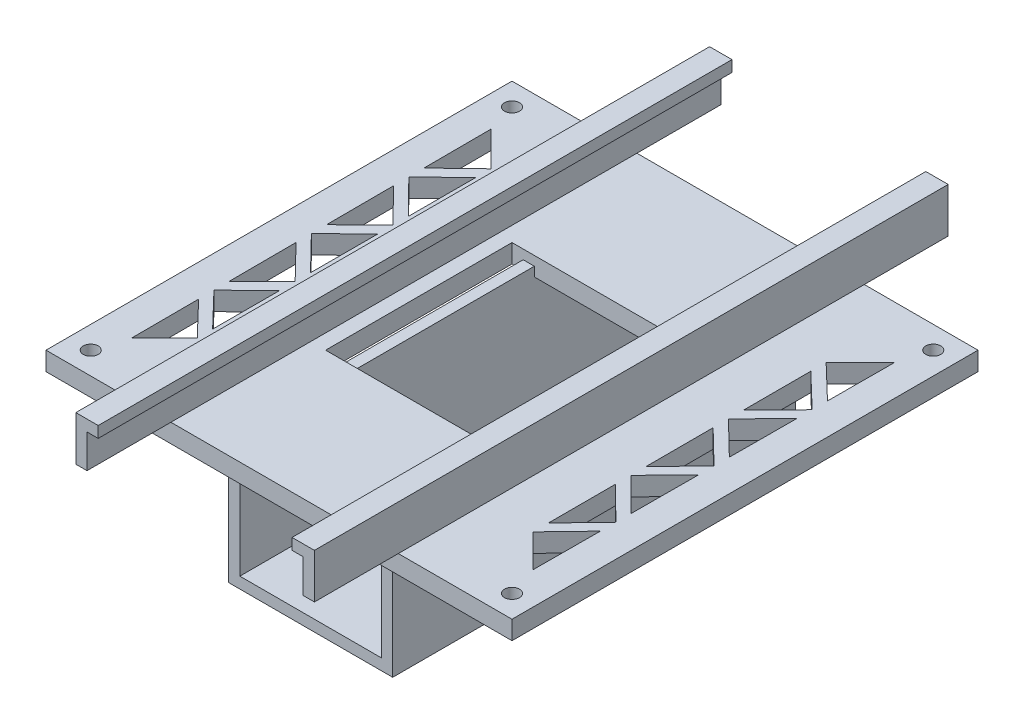
SolidWorks part; units mm, degrees
other "마크업1"
sketch "스케치10" plane through (-62.5, -31.5, -62.5) normal (-0.0294, -0.9842, -0.1746) x (0.6542, 0.1131, -0.7478)
ref_plane "정면" through (0, 0, 0) normal (0, 0, 1) x (1, 0, 0)
ref_plane "윗면" through (0, 0, 0) normal (0, 1, 0) x (1, 0, 0)
ref_plane "우측면" through (0, 0, 0) normal (1, 0, 0) x (0, 0, -1)
ref_axis "기준축1" through (0, 4.2, 0) along (0, -1, 0)
sketch "스케치2" plane through (0, 0, 0) normal (0, 1, 0) x (1, 0, 0)
  line L1 (62.5, 62.5) -> (-62.5, 62.5)
  line L2 (62.5, 62.5) -> (62.5, -62.5)
  line L3 (62.5, -62.5) -> (-62.5, -62.5)
  line L4 (-62.5, 62.5) -> (-62.5, -62.5)
  line L5 (62.5, 62.5) -> (-62.5, -62.5) construction
  line L6 (62.5, -62.5) -> (-62.5, 62.5) construction
  line L7 (-25, 25) -> (25, 25)
  line L8 (-25, 25) -> (-25, -25)
  line L9 (-25, -25) -> (25, -25)
  line L10 (25, 25) -> (25, -25)
  line L11 (-25, 25) -> (25, -25) construction
  line L12 (-25, -25) -> (25, 25) construction
  circle A0 centre (-56.5, 56.5) radius 2
  circle A1 centre (56.5, 56.5) radius 2
  circle A2 centre (-56.5, -56.5) radius 2
  circle A3 centre (56.5, -56.5) radius 2
  point P0 (0, 0)
  point P6 (0, 0)
  dimension "D5" = 4
  dimension "D1" = 125
  dimension "D2" = 125
  dimension "D3" = 50
  dimension "D4" = 50
  dimension "D6" = 6
  dimension "D7" = 6
  dimension "D8" = 6
  dimension "D9" = 6
extrude "보스-돌출1" add sketch "스케치2" along normal mid plane 5
sketch "스케치6" plane through (0, 0, 0) normal (0, 0, 1) x (1, 0, 0)
  line L0 (0, 0) -> (50000, 0) construction
  line L2 (0, 0) -> (0, -50000) construction
  line L3 (-22, 0) -> (-22, -35.5)
  line L4 (-22, -35.5) -> (22, -35.5)
  line L6 (19, -32.5) -> (-19, -32.5)
  line L7 (-19, -32.5) -> (-19, 0)
  line L8 (-19, 0) -> (-22, 0)
  line L9 (19, 0) -> (22, 0)
  line L10 (19, -32.5) -> (19, 0)
  line L11 (22, 0) -> (22, -35.5)
  line L12 (-62.5, -2.5) -> (62.5, -2.5) construction
  point P14 (0, -32.5)
  point P15 (0, -35.5)
  dimension "D1" = 38
  dimension "D2" = 3
  dimension "D3" = 30
  dimension "D4" = 3
extrude "보스-돌출4" add sketch "스케치6" along normal mid plane 108
sketch "스케치11" plane through (0, 0, 0) normal (0, 0, 1) x (1, 0, 0)
  line L0 (-32, 2.5) -> (-32, 14.5)
  line L1 (-62.5, 2.5) -> (62.5, 2.5) construction
  line L2 (-32, 14.5) -> (-26, 14.5)
  line L3 (-26, 14.5) -> (-26, 11.5)
  line L4 (-26, 11.5) -> (-29, 11.5)
  line L5 (-29, 11.5) -> (-29, 2.5)
  line L6 (-32, 2.5) -> (-29, 2.5)
  line L7 (0, -25.3) -> (0, 25.3) construction
  line L8 (32, 2.5) -> (29, 2.5)
  line L9 (29, 11.5) -> (29, 2.5)
  line L10 (26, 11.5) -> (29, 11.5)
  line L11 (26, 14.5) -> (26, 11.5)
  line L12 (32, 14.5) -> (26, 14.5)
  line L13 (32, 2.5) -> (32, 14.5)
  point P8 (-26, 13)
  dimension "D1" = 29
  dimension "D2" = 3
  dimension "D3" = 9
  dimension "D4" = 3
  dimension "D5" = 6
sketch "스케치7" plane through (0, 0, 0) normal (0, 1, 0) x (1, 0, 0)
  line L1 (-40, 40) -> (40, 40)
  line L2 (-40, 40) -> (-40, -40)
  line L3 (-40, -40) -> (40, -40)
  line L4 (40, 40) -> (40, -40)
  line L5 (-40, 40) -> (40, -40) construction
  line L6 (-40, -40) -> (40, 40) construction
  point P0 (0, 0)
  dimension "D1" = 80
  dimension "D2" = 80
extrude "컷-돌출1" [suppressed] cut sketch "스케치7" along normal blind 10
sketch "스케치8" plane through (0, 2.5, 0) normal (0, 1, 0) x (1, 0, 0)
  line L14 (54.1085, 30.5155) -> (54.094, 26.4186) construction
  line L15 (54.0793, 22.2856) -> (54.0155, 4.2857)
  line L20 (44.9633, 35.1872) -> (44.959, 39.3022) construction
  line L41 (53.8296, -48.1728) -> (45.0411, -39.3843)
  line L42 (45.0368, -35.2728) -> (45.018, -17.2728)
  line L43 (44.959, 39.3022) -> (54.1723, 48.5154)
  line L44 (54.1723, 48.5154) -> (54.1085, 30.5155)
  line L83 (62.5, -62.5) -> (-62.5, 62.5) construction
  line L94 (62.5, 62.5) -> (-62.5, -62.5) construction
  line L96 (45.0411, -39.3843) -> (53.8934, -30.1704)
  line L97 (45.0368, -35.2728) -> (53.9081, -26.0392)
  line L98 (53.9081, -26.0392) -> (45.018, -17.2728)
  line L100 (53.9226, -21.9404) -> (45.0138, -13.1555)
  line L101 (45.0138, -13.1555) -> (53.9864, -3.9443)
  line L103 (45.0095, -9.0428) -> (54.001, 0.1878)
  line L104 (54.001, 0.1878) -> (44.9907, 8.9572)
  line L106 (44.9864, 13.0733) -> (54.0155, 4.2857)
  line L107 (44.9864, 13.0733) -> (54.0793, 22.2856)
  line L108 (44.9821, 17.1872) -> (54.094, 26.4186)
  line L110 (54.094, 26.4186) -> (44.9633, 35.1872)
  line L112 (54.1085, 30.5155) -> (44.959, 39.3022)
  line L113 (44.9864, 13.0733) -> (44.9821, 17.1872) construction
  line L114 (44.9821, 17.1872) -> (44.9633, 35.1872)
  line L115 (54.094, 26.4186) -> (54.0793, 22.2856) construction
  line L116 (44.9907, 8.9572) -> (44.9864, 13.0733) construction
  line L117 (54.001, 0.1878) -> (53.9864, -3.9443) construction
  line L118 (53.9864, -3.9443) -> (53.9226, -21.9404)
  line L119 (54.0155, 4.2857) -> (54.001, 0.1878) construction
  line L120 (45.0138, -13.1555) -> (45.0095, -9.0428) construction
  line L121 (45.0095, -9.0428) -> (44.9907, 8.9572)
  line L122 (45.0411, -39.3843) -> (45.0368, -35.2728) construction
  line L123 (53.9081, -26.0392) -> (53.8934, -30.1704) construction
  line L124 (53.8934, -30.1704) -> (53.8296, -48.1728)
  line L125 (53.9226, -21.9404) -> (53.9081, -26.0392) construction
  line L126 (45.018, -17.2728) -> (45.0138, -13.1555) construction
  line L146 (0, -25.3) -> (0, 25.3) construction
  line L155 (-45.018, -17.2728) -> (-45.0138, -13.1555) construction
  line L156 (-53.9226, -21.9404) -> (-53.9081, -26.0392) construction
  line L157 (-53.9081, -26.0392) -> (-53.8934, -30.1704) construction
  line L158 (-45.0411, -39.3843) -> (-45.0368, -35.2728) construction
  line L159 (-45.0138, -13.1555) -> (-45.0095, -9.0428) construction
  line L160 (-54.0155, 4.2857) -> (-54.001, 0.1878) construction
  line L161 (-54.001, 0.1878) -> (-53.9864, -3.9443) construction
  line L162 (-44.9907, 8.9572) -> (-44.9864, 13.0733) construction
  line L163 (-54.094, 26.4186) -> (-54.0793, 22.2856) construction
  line L164 (-44.9864, 13.0733) -> (-44.9821, 17.1872) construction
  line L165 (-44.9633, 35.1872) -> (-44.959, 39.3022) construction
  line L166 (-54.1085, 30.5155) -> (-54.094, 26.4186) construction
  line L178 (-53.8934, -30.1704) -> (-53.8296, -48.1728)
  line L179 (-45.0095, -9.0428) -> (-44.9907, 8.9572)
  line L180 (-53.9864, -3.9443) -> (-53.9226, -21.9404)
  line L181 (-44.9821, 17.1872) -> (-44.9633, 35.1872)
  line L182 (-54.1085, 30.5155) -> (-44.959, 39.3022)
  line L183 (-54.094, 26.4186) -> (-44.9633, 35.1872)
  line L184 (-44.9821, 17.1872) -> (-54.094, 26.4186)
  line L185 (-44.9864, 13.0733) -> (-54.0793, 22.2856)
  line L186 (-44.9864, 13.0733) -> (-54.0155, 4.2857)
  line L187 (-54.001, 0.1878) -> (-44.9907, 8.9572)
  line L188 (-45.0095, -9.0428) -> (-54.001, 0.1878)
  line L189 (-45.0138, -13.1555) -> (-53.9864, -3.9443)
  line L190 (-53.9226, -21.9404) -> (-45.0138, -13.1555)
  line L191 (-53.9081, -26.0392) -> (-45.018, -17.2728)
  line L192 (-45.0368, -35.2728) -> (-53.9081, -26.0392)
  line L193 (-45.0411, -39.3843) -> (-53.8934, -30.1704)
  line L194 (-54.1723, 48.5154) -> (-54.1085, 30.5155)
  line L195 (-44.959, 39.3022) -> (-54.1723, 48.5154)
  line L196 (-45.0368, -35.2728) -> (-45.018, -17.2728)
  line L197 (-53.8296, -48.1728) -> (-45.0411, -39.3843)
  line L202 (-54.0793, 22.2856) -> (-54.0155, 4.2857)
  dimension "D3" = 45
  dimension "D4" = 54
  dimension "D5" = 4
  dimension "D6" = 4
  dimension "D9" = 8.23
  dimension "D10" = 4.115
  dimension "D11" = 18
  dimension "D7" = 18
  dimension "D13" = 8.23
  dimension "D14" = 18
  dimension "D16" = 8.23
  dimension "D17" = 18
  dimension "D19" = 8.23
  dimension "D20" = 8.23
  dimension "D21" = 17.9963
  dimension "D22" = 18
  dimension "D23" = 18.0024
extrude "컷-돌출2" cut sketch "스케치8" against normal blind 5 and the other way through all
pattern_circular "원형 패턴1" [suppressed] count 4 over 360 about axis through (0, 4.2, 0) along (0, -1, 0) of bodies 108
extrude "보스-돌출7" add sketch "스케치11" along normal mid plane 170
sketch "스케치9" [suppressed] plane through (0, 2.5, 0) normal (0, 1, 0) x (1, 0, 0)
  line L0 (-39.3431, -45) -> (-49.8431, -55.5)
  line L1 (-49.8431, -55.5) -> (-24, -55.5)
  line L2 (-24, -55.5) -> (-24, -45)
  line L3 (-24, -45) -> (-39.3431, -45)
  line L4 (62.5, -62.5) -> (-62.5, -62.5) construction
  line L5 (-40, -40) -> (40, -40) construction
  line L6 (62.5, 62.5) -> (-62.5, -62.5) construction
  line L7 (-20, -25) -> (-20, 25) construction
  line L8 (0, -18.7) -> (0, 18.7) construction
  line L9 (24, -45) -> (39.3431, -45)
  line L10 (24, -55.5) -> (24, -45)
  line L11 (49.8431, -55.5) -> (24, -55.5)
  line L12 (39.3431, -45) -> (49.8431, -55.5)
  line L13 (-18.7, 0) -> (18.7, 0) construction
  line L14 (39.3431, 45) -> (49.8431, 55.5)
  line L15 (49.8431, 55.5) -> (24, 55.5)
  line L16 (24, 55.5) -> (24, 45)
  line L17 (24, 45) -> (39.3431, 45)
  line L18 (-24, 45) -> (-39.3431, 45)
  line L19 (-24, 55.5) -> (-24, 45)
  line L20 (-49.8431, 55.5) -> (-24, 55.5)
  line L21 (-39.3431, 45) -> (-49.8431, 55.5)
  dimension "D1" = 7
  dimension "D2" = 5
  dimension "D3" = 4
  dimension "D4" = 4
extrude "컷-돌출3" [suppressed] cut sketch "스케치9" against normal through all
